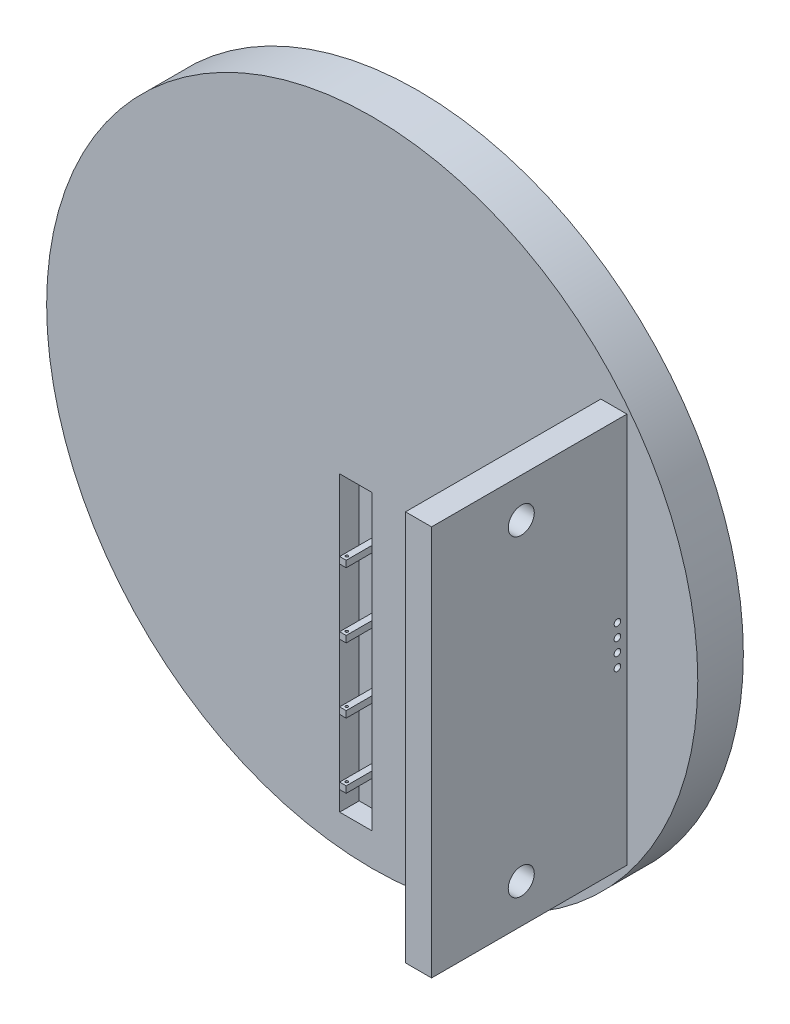
SolidWorks part; units mm, degrees
ref_plane "Front Plane" through (0, 0, 0) normal (1, 0, 0) x (0, 1, 0)
ref_plane "Top Plane" through (0, 0, 0) normal (0, 0, 1) x (0, 1, 0)
ref_plane "Right Plane" through (0, 0, 0) normal (0, 1, 0) x (-1, 0, 0)
sketch "Sketch2" plane through (0, 0, 0) normal (0, 0, 1) x (0, 1, 0)
  circle A0 centre (0, 0) radius 25
  dimension "D1" = 50
extrude "Boss-Extrude1" add sketch "Sketch2" along normal blind 2.5
sketch "Sketch4" plane through (0, 0, 0) normal (0, 1, 0) x (-1, 0, 0)
  line L8 (-25, 0) -> (25, 0) construction
  line L9 (0, 1) -> (2.5, 1)
  line L10 (0, 1) -> (0, 3.7269)
  line L11 (0, 3.7269) -> (2.5, 3.7269)
  line L12 (2.5, 1) -> (2.5, 3.7269)
  line L13 (0, 0) -> (0, 9.8399) construction
  dimension "D1" = 2.5
  dimension "D2" = 1
extrude "Cut-Extrude1" cut sketch "Sketch4" against normal blind 22.5
sketch "Sketch8" plane through (0, 0, 0) normal (1, 0, 0) x (0, 1, 0)
  line L0 (-25, 0) -> (25, 0) construction
  line L1 (2, 0) -> (3, 0)
  line L2 (2, 0) -> (2, -1)
  line L3 (2, -1) -> (3, -1)
  line L4 (3, 0) -> (3, -1)
  line L5 (0, 0) -> (0, 4.9151) construction
  line L6 (4, 0) -> (4, -1)
  line L7 (4, 0) -> (5, 0)
  line L8 (5, 0) -> (5, -1)
  line L9 (4, -1) -> (5, -1)
  line L10 (6, 0) -> (6, -1)
  line L11 (6, 0) -> (7, 0)
  line L12 (7, 0) -> (7, -1)
  line L13 (6, -1) -> (7, -1)
  line L14 (8, 0) -> (8, -1)
  line L15 (8, 0) -> (9, 0)
  line L16 (9, 0) -> (9, -1)
  line L17 (8, -1) -> (9, -1)
  line L19 (25, 0) -> (23, 0)
  line L20 (25, 0) -> (25, -1)
  line L21 (25, -1) -> (23, -1)
  line L22 (23, 0) -> (23, -1)
  point P26 (4, -0.5)
  dimension "D1" = 1
  dimension "D2" = 2
  dimension "D3" = 1
  dimension "D5" = 1
  dimension "D6" = 2
  dimension "D7" = 1
  dimension "D4" = 4
revolve "Revolve2" add sketch "Sketch8" angle 360 about L5
sketch "Sketch9" plane through (0, 0, 0) normal (0, 0, 1) x (0, 1, 0)
  line L1 (-5, 1.5) -> (-4.5, 1.5)
  line L2 (-5, 1.5) -> (-5, 1)
  line L3 (-5, 1) -> (-4.5, 1)
  line L4 (-4.5, 1.5) -> (-4.5, 1)
  line L5 (0, 2.5) -> (-22.5, 2.5) construction
  line L6 (0, 2.5) -> (0, 0) construction
  line L7 (-10, 1.5) -> (-10, 1)
  line L8 (-10, 1.5) -> (-9.5, 1.5)
  line L9 (-9.5, 1.5) -> (-9.5, 1)
  line L10 (-10, 1) -> (-9.5, 1)
  line L11 (-15, 1.5) -> (-15, 1)
  line L12 (-15, 1.5) -> (-14.5, 1.5)
  line L13 (-14.5, 1.5) -> (-14.5, 1)
  line L14 (-15, 1) -> (-14.5, 1)
  line L15 (-20, 1.5) -> (-20, 1)
  line L16 (-20, 1.5) -> (-19.5, 1.5)
  line L17 (-19.5, 1.5) -> (-19.5, 1)
  line L18 (-20, 1) -> (-19.5, 1)
  dimension "D1" = 0.5
  dimension "D2" = 1
  dimension "D3" = 0.5
  dimension "D4" = 4.5
  dimension "D5" = 4
extrude "Boss-Extrude3" add sketch "Sketch9" along normal blind 3.5
sketch "Sketch10" plane through (0, -20, 0) normal (0, -1, 0) x (1, 0, 0)
  line L0 (-1.25, 3.5) -> (-1.25, 2.7375) construction
  line L4 (-1.5, 3.5) -> (-1, 3.5) construction
  circle A0 centre (-1.25, 3.202) radius 0.1
  point P3 (-1.5, 3.4191)
  point P4 (-1.5, 3.5)
  dimension "D1" = 0.2
extrude "Cut-Extrude2" cut sketch "Sketch10" against normal blind 17.5
sketch "Sketch11" plane through (0, 0, 2.5) normal (0, 0, 1) x (1, 0, 0)
  line L0 (0, 0) -> (35.7105, 0) construction
  line L10 (17.5585, 15) -> (19.5585, 15)
  line L11 (17.5585, 15) -> (17.5585, -15)
  line L12 (17.5585, -15) -> (19.5585, -15)
  line L13 (19.5585, 15) -> (19.5585, -15)
  dimension "D1" = 30
  dimension "D2" = 15
  dimension "D3" = 2
extrude "Boss-Extrude4" add sketch "Sketch11" along normal blind 15
sketch "Sketch12" plane through (19.5585, 0, 0) normal (1, 0, 0) x (0, 1, 0)
  line L0 (0, 17.5) -> (0, -5.9778) construction
  line L1 (-15, 17.5) -> (15, 17.5) construction
  circle A0 centre (12, 10.6132) radius 1
  circle A1 centre (-12, 10.6132) radius 1
  circle A2 centre (0.5, 3.2297) radius 0.25
  circle A3 centre (1.5, 3.2297) radius 0.25
  circle A4 centre (-1.5, 3.2297) radius 0.25
  circle A5 centre (-0.5, 3.2297) radius 0.25
  dimension "D1" = 2
  dimension "D4" = 0.5
  dimension "D2" = 12
  dimension "D3" = 0.5
  dimension "D5" = 2
extrude "Cut-Extrude3" cut sketch "Sketch12" against normal blind 15
